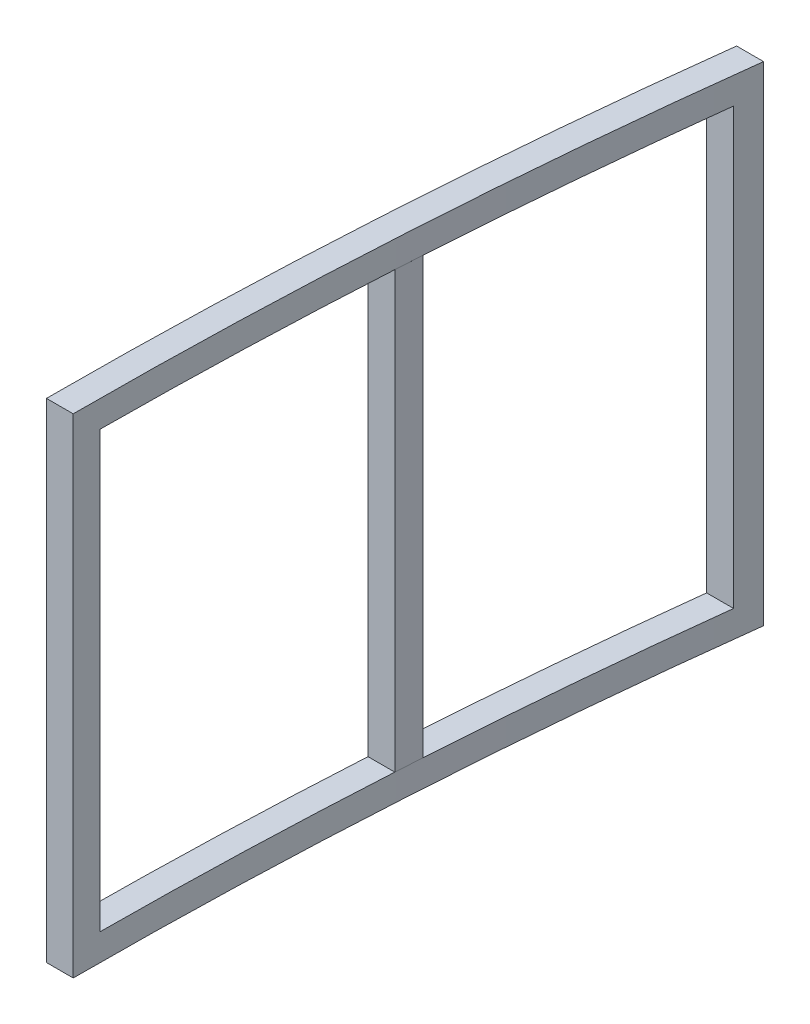
SolidWorks part; units mm, degrees
ref_plane "Front" through (0, 0, 0) normal (0, 0, 1) x (1, 0, 0)
ref_plane "Top" through (0, 0, 0) normal (0, 1, 0) x (1, 0, 0)
ref_plane "Right" through (0, 0, 0) normal (1, 0, 0) x (0, 0, -1)
sketch "Sketch1" plane through (0, 0, 0) normal (0, 1, 0) x (1, 0, 0)
  line L1 (-9820.6446, 1216.8845) -> (-9871.1258, 1216.8845)
  line L2 (-9895.75, 0) -> (-9945.85, 0)
  arc A0 (-9820.6446, 1216.8845) -> (-9895.75, 0) centre (0, 0) ccw
  arc A1 (-9871.1258, 1216.8845) -> (-9945.85, 0) centre (0, 0) ccw
  dimension "D1" = 19791.5
  dimension "D2" = 19891.7
  dimension "D3" = 1219.2
extrude "Boss-Extrude1" add sketch "Sketch1" along normal blind 914.4
ref_plane "Plane1" through (9945.85, 0, 0) normal (1, 0, 0) x (0, 0, -1)
sketch "Sketch2" plane through (9945.85, 0, 0) normal (1, 0, 0) x (0, 0, -1)
  line L1 (0, 0) -> (1216.8845, 0) construction
  line L2 (0, 0) -> (0, 914.4) construction
  line L3 (0, 914.4) -> (1216.8845, 914.4) construction
  line L4 (1216.8845, 0) -> (1216.8845, 914.4) construction
  line L5 (1166.8845, 864.4) -> (50, 864.4)
  line L6 (1166.8845, 864.4) -> (1166.8845, 50)
  line L7 (1166.8845, 50) -> (50, 50)
  line L8 (50, 864.4) -> (50, 50)
  line L9 (1166.8845, 864.4) -> (50, 50) construction
  line L10 (1166.8845, 50) -> (50, 864.4) construction
  point P6 (608.4422, 457.2)
  dimension "D1" = 50
  dimension "D2" = 50
  dimension "D3" = 50
  dimension "D4" = 50
extrude "Cut-Extrude1" cut sketch "Sketch2" against normal through all
sketch "Sketch5" plane through (0, 864.4, 0) normal (0, -1, 0) x (1, 0, 0)
  line L0 (-9925.5839, -634.6) -> (-9875.3811, -634.6)
  line L1 (-9928.6542, -584.6) -> (-9878.467, -584.6)
  line L2 (-9895.75, 0) -> (-9820.6446, -1216.8845) construction
  line L3 (-9928.6542, -584.6) -> (-9925.5839, -634.6)
  line L4 (-9878.467, -584.6) -> (-9875.3811, -634.6)
  arc A0 (-9945.85, 0) -> (-9871.1258, -1216.8845) centre (0, 0) ccw construction
  arc A1 (-9895.75, 0) -> (-9820.6446, -1216.8845) centre (0, 0) ccw construction
  dimension "D1" = 50
  dimension "D2" = 584.6
extrude "Boss-Extrude3" add sketch "Sketch5" along normal blind 814.4
equation "\"inside\"= 9895.75 * 2"
equation "\"D1@Sketch1\"=\"inside\""
equation "\"outside\"= 9945.85 * 2"
equation "\"D2@Sketch1\"=\"outside\""
equation "\"cut\"=1219.2"
equation "\"centeringline\"=584.6"
equation "\"D2@Sketch5\"=\"centeringline\""
equation "\"framewidth\"=50"
equation "\"D1@Sketch5\"=\"framewidth\""
